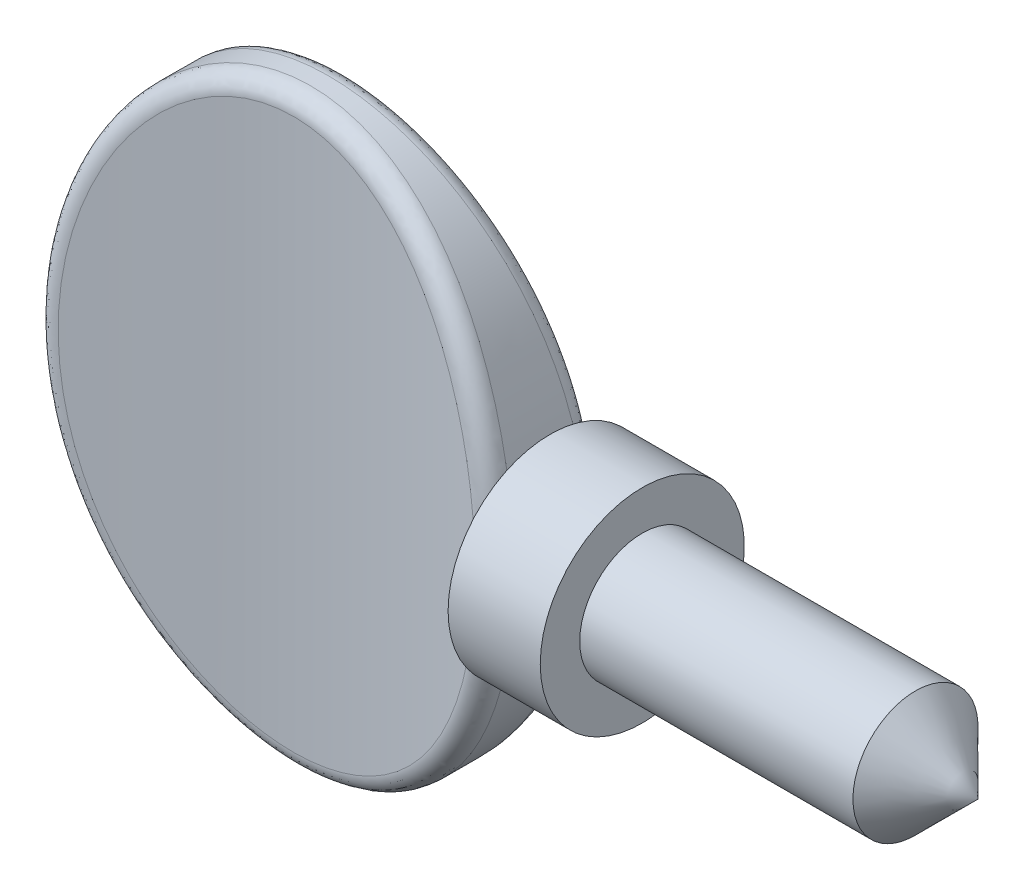
SolidWorks part; units mm, degrees
ref_plane "Front" through (0, 0, 0) normal (0, 0, 1) x (1, 0, 0)
ref_plane "Top" through (0, 0, 0) normal (0, 1, 0) x (1, 0, 0)
ref_plane "Right" through (0, 0, 0) normal (1, 0, 0) x (0, 0, -1)
ref_axis "Axis1" through (-50, 0, 0) along (1, 0, 0)
sketch "Sketch1" plane through (0, 0, 0) normal (0, 0, 1) x (1, 0, 0)
  line L0 (0, 0) -> (25.4, 0) construction
  line L1 (12.446, -3.937) -> (12.446, 3.937)
  ellipse E0 centre (0, 0) end of major axis (0, 11.303) minor radius 8.89
  dimension "D2" = 3.556
extrude "Extrude1" add sketch "Sketch1" along normal mid plane 4.572
sketch "Sketch2" plane through (0, 0, 0) normal (0, 1, 0) x (1, 0, 0)
  line L0 (8.89, 2.286) -> (-8.89, 2.286) construction
  line L1 (0, 0) -> (0, 1.1721) construction
  line L2 (-1.7991, 0) -> (2.0444, 0) construction
  line L3 (-8.89, -2.286) -> (8.89, -2.286) construction
  line L6 (-8.89, 2.286) -> (-8.89, -2.286)
  line L7 (8.89, 2.286) -> (8.89, -2.286)
  arc A0 (-8.89, 2.286) -> (8.89, 2.286) centre (0, 32.766) ccw
  arc A1 (-8.89, -2.286) -> (8.89, -2.286) centre (0, -32.766) cw
extrude "Cut-Extrude1" cut sketch "Sketch2" against normal through all and the other way through all flip side to cut
fillet "Fillet3" radius 0.6773 2 edges at (-8.875, -0.6558, 2.2816) (-1.5369, -11.1328, -1.0532)
sketch "Sketch3" plane through (0, 0, 0) normal (0, 1, 0) x (1, 0, 0)
  line L0 (12.446, 3.937) -> (12.446, 2.413)
  line L1 (0, 0) -> (18.8263, 0) construction
  line L2 (0, 0) -> (25.4, 0) construction
  line L3 (12.446, 2.413) -> (12.446, 0) construction
  line L4 (12.446, 2.413) -> (22.987, 2.413)
  line L5 (22.987, 2.413) -> (25.4, 0)
  line L6 (12.446, 3.937) -> (8.89, 3.937)
  line L7 (7.2364, 1.8517) -> (7.2364, 0)
  line L8 (8.89, 0) -> (8.89, 3.937) construction
  line L9 (7.2364, 0) -> (25.4, 0)
  arc A0 (8.89, 3.937) -> (7.2364, 1.8517) centre (6.7483, 3.937) cw
  arc A3 (-8.89, 2.286) -> (8.89, 2.286) centre (0, 32.766) ccw construction
  dimension "D1" = 7.874
  dimension "D2" = 45
revolve "Revolve1" add sketch "Sketch3" angle 360 about L0
cosmetic thread "Cosmetic Thread1" [suppressed]
sketch "Sketch4" plane through (0, 0, 0) normal (0, 0, 1) x (1, 0, 0)
  line L0 (0, 0) -> (27.7993, 0) construction
  line L1 (22.6233, 2.413) -> (22.987, 1.7831)
  line L2 (22.987, 1.7831) -> (23.3507, 2.413)
  line L3 (23.3507, 2.413) -> (23.3507, 3.1404)
  line L4 (23.3507, 3.1404) -> (22.6233, 3.1404)
  line L5 (22.6233, 3.1404) -> (22.6233, 2.413)
  line L6 (22.987, 2.413) -> (22.987, -2.413) construction
  dimension "D1" = 3.5662
  dimension "D2" = 4.826
revolve "Cut-Revolve10" [suppressed] cut sketch "Sketch4" angle 360 about L0
pattern_linear "LPattern10" [suppressed] count 10 along (-1, 0, 0) of bodies 109
equation "\"D2@Sketch1\" = \"B@Sketch1\" / 6"
equation "\"D1@Sketch3\" = \"E@Sketch1\""
equation "\"D1@Fillet3\" = \"C1@Sketch2\" / 3"
equation "\"D1@Sketch4\" = \"D2@Cosmetic Thread1\""
equation "\"D2@Sketch4\" = \"DIA@Sketch3\""
equation "\"D1@LPattern10\" = (  \"L@Sketch1\"-\"DIA@Sketch3\" / 2 )  / \"P@LPattern10\" "
